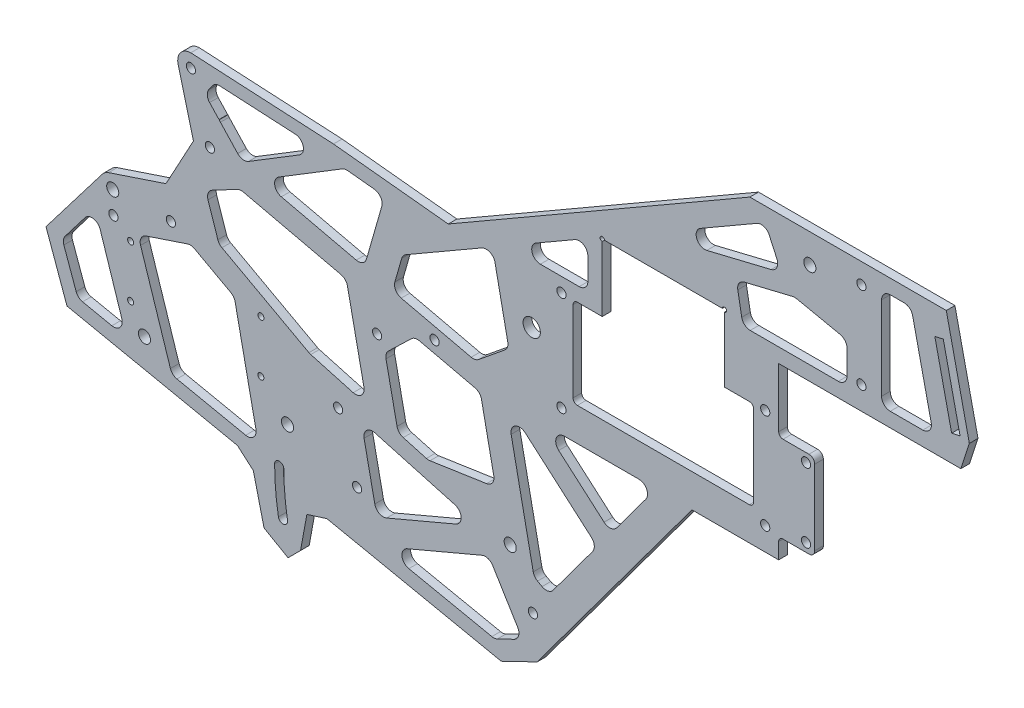
SolidWorks part; units mm, degrees
material "6061 Alloy"
ref_plane "Front Plane" through (0, 0, 0) normal (0, 0, 1) x (1, 0, 0)
ref_plane "Top Plane" through (0, 0, 0) normal (0, 1, 0) x (1, 0, 0)
ref_plane "Right Plane" through (0, 0, 0) normal (1, 0, 0) x (0, 0, -1)
sketch "Sketch1" plane through (0, 0, 0) normal (0, 0, 1) x (1, 0, 0)
  line L1 (-20.4587, 47.6) -> (-183.6375, 47.6)
  line L2 (-20.4587, 47.6) -> (-20.4587, -36.0143)
  line L3 (-20.4587, -36.0143) -> (-183.6375, -36.0143)
  line L4 (-183.6375, 47.6) -> (-183.6375, -36.0143)
extrude "Boss-Extrude1" add sketch "Sketch1" along normal blind 3
sketch "Sketch2" plane through (0, 0, 3) normal (0, 0, 1) x (1, 0, 0)
  circle A0 centre (-24.2887, 24) radius 3
  dimension "D1" = 6
extrude "Cut-Extrude1" cut sketch "Sketch2" against normal blind 70
sketch "Sketch3" plane through (0, 0, 3) normal (0, 0, 1) x (1, 0, 0)
  line L4 (-20.4587, -36.0143) -> (-20.4587, 47.6)
  line L5 (-20.4587, 47.6) -> (-183.6375, 47.6)
  line L6 (-183.6375, 47.6) -> (-183.6375, -36.0143)
  line L7 (-183.6375, -36.0143) -> (-20.4587, -36.0143)
  line L8 (-20.4587, -36.0143) -> (-20.4587, 47.6)
  line L9 (-20.4587, 47.6) -> (-41.1202, 47.6)
  line L10 (-183.6375, 47.6) -> (-183.6375, -36.0143)
  line L11 (-183.6375, -36.0143) -> (-20.4587, -36.0143)
  line L13 (51.3713, 101) -> (-41.1202, 47.6)
  line L14 (-41.1202, 47.6) -> (-120.7247, 47.6)
  line L15 (-204.873, 47.6) -> (-204.873, -81.5667)
  line L16 (-204.873, -81.5667) -> (-34.873, -81.5667)
  line L17 (-34.873, -81.5667) -> (61.3713, -26)
  line L18 (61.3713, -26) -> (61.3713, 2.5)
  line L19 (62.8713, 4) -> (71.8713, 4)
  line L20 (73.8713, 6) -> (73.8713, 32)
  line L21 (71.8713, 34) -> (62.8713, 34)
  line L22 (61.3713, 35.5) -> (61.3713, 56)
  line L23 (61.3713, 56) -> (121.3713, 56)
  line L24 (121.3713, 56) -> (121.3713, 101)
  line L25 (121.3713, 101) -> (51.3713, 101)
  line L26 (51.3713, 101) -> (-41.1202, 47.6)
  line L27 (-167.8527, 47.6) -> (-120.7247, 47.6)
  line L28 (-204.873, 47.6) -> (-204.873, -81.5667)
  line L29 (-204.873, -81.5667) -> (-34.873, -81.5667)
  line L30 (-34.873, -81.5667) -> (61.3713, -26)
  line L31 (61.3713, -26) -> (61.3713, 2.5)
  line L32 (62.8713, 4) -> (71.8713, 4)
  line L33 (73.8713, 6) -> (73.8713, 32)
  line L34 (71.8713, 34) -> (62.8713, 34)
  line L35 (61.3713, 35.5) -> (61.3713, 56)
  line L36 (61.3713, 56) -> (121.3713, 56)
  line L37 (121.3713, 56) -> (121.3713, 101)
  line L38 (121.3713, 101) -> (51.3713, 101)
  line L265 (-167.8527, 47.6) -> (-204.873, 47.6)
  line L266 (-183.6375, 47.6) -> (-204.873, 47.6)
  circle A0 centre (70.8713, 31) radius 1.6 construction
  circle A1 centre (70.8713, 7) radius 1.6 construction
  arc A2 (71.8713, 4) -> (73.8713, 6) centre (71.8713, 6) ccw
  arc A3 (73.8713, 32) -> (71.8713, 34) centre (71.8713, 32) ccw
  arc A4 (71.8713, 4) -> (73.8713, 6) centre (71.8713, 6) ccw
  arc A5 (73.8713, 32) -> (71.8713, 34) centre (71.8713, 32) ccw
  circle A6 centre (70.8713, 31) radius 1.6
  circle A7 centre (70.8713, 7) radius 1.6
  arc A38 (62.8713, 4) -> (61.3713, 2.5) centre (62.8713, 2.5) ccw
  arc A39 (62.8713, 4) -> (61.3713, 2.5) centre (62.8713, 2.5) ccw
  arc A40 (61.3713, 35.5) -> (62.8713, 34) centre (62.8713, 35.5) ccw
  arc A41 (61.3713, 35.5) -> (62.8713, 34) centre (62.8713, 35.5) ccw
  arc A60 (-120.7247, 47.6) -> (-167.8527, 47.6) centre (-144.2887, 24) ccw
  arc A61 (-120.7247, 47.6) -> (-167.8527, 47.6) centre (-144.2887, 24) ccw
  dimension "D1" = 0
  dimension "D2" = 0
extrude "Boss-Extrude2" add sketch "Sketch3" against normal blind 3
sketch "Sketch4" plane through (0, 0, 3) normal (0, 0, 1) x (1, 0, 0)
  line L0 (0.1713, 62.05) -> (0.1713, 39.5) construction
  line L2 (-9.9587, 10) -> (-9.9587, 38) construction
  line L3 (-8.4587, 8.5) -> (51.2013, 8.5) construction
  line L4 (52.7013, 10) -> (52.7013, 38) construction
  line L7 (41.8213, 62.8) -> (0.9213, 62.8) construction
  line L8 (0.1713, 62.05) -> (0.1713, 39.5)
  line L9 (-8.4587, 39.5) -> (0.1713, 39.5)
  line L10 (-9.9587, 10) -> (-9.9587, 38)
  line L11 (-8.4587, 8.5) -> (51.2013, 8.5)
  line L12 (52.7013, 10) -> (52.7013, 38)
  line L13 (42.5713, 39.5) -> (51.2013, 39.5)
  line L14 (42.5713, 62.05) -> (42.5713, 39.5)
  line L15 (41.8213, 62.8) -> (0.9213, 62.8)
  arc A1 (-8.4587, 39.5) -> (-9.9587, 38) centre (-8.4587, 38) ccw construction
  arc A2 (-9.9587, 10) -> (-8.4587, 8.5) centre (-8.4587, 10) ccw construction
  arc A3 (51.2013, 8.5) -> (52.7013, 10) centre (51.2013, 10) ccw construction
  arc A4 (52.7013, 38) -> (51.2013, 39.5) centre (51.2013, 38) ccw construction
  arc A5 (42.5713, 62.05) -> (41.8213, 62.8) centre (42.5713, 62.8) ccw construction
  arc A6 (0.9213, 62.8) -> (0.1713, 62.05) centre (0.1713, 62.8) ccw
  arc A7 (-8.4587, 39.5) -> (-9.9587, 38) centre (-8.4587, 38) ccw
  arc A8 (-9.9587, 10) -> (-8.4587, 8.5) centre (-8.4587, 10) ccw
  arc A9 (51.2013, 8.5) -> (52.7013, 10) centre (51.2013, 10) ccw
  arc A10 (52.7013, 38) -> (51.2013, 39.5) centre (51.2013, 38) ccw
  arc A11 (42.5713, 62.05) -> (41.8213, 62.8) centre (42.5713, 62.8) ccw
extrude "Cut-Extrude2" cut sketch "Sketch4" against normal blind 10
sketch "Sketch6" plane through (0, 0, 0) normal (0, 0, -1) x (-1, 0, 0)
  line L0 (-121.3713, 101) -> (-51.3713, 101) construction
  line L1 (-121.3713, 56) -> (-121.3713, 101) construction
  line L2 (204.873, -81.5667) -> (34.873, -81.5667) construction
  line L3 (-61.3713, -26) -> (-61.3713, 2.5) construction
  line L4 (204.873, 47.6) -> (204.873, -81.5667) construction
  circle A2 centre (158.6381, -45.9257) radius 2.1
  circle A3 centre (169.6384, -7.2338) radius 2.1
  circle A4 centre (109.0119, -47.5134) radius 2.1
  circle A5 centre (31.7556, -45.033) radius 2.1
  circle A6 centre (-71.9717, 91) radius 2.1
  dimension "D1" = 10
  dimension "D2" = 49.3996
  dimension "D3" = 36.5337
  dimension "D4" = 93.1269
  dimension "D5" = 34.0533
  dimension "D6" = 95.8611
  dimension "D7" = 35.641
  dimension "D8" = 46.2349
  dimension "D9" = 35.2346
  dimension "D10" = 74.3329
  dimension "D11" = 4.2
extrude "Cut-Extrude3" cut sketch "Sketch6" against normal blind 10
sketch "Sketch7" plane through (0, 0, 3) normal (0, 0, 1) x (1, 0, 0)
  circle A0 centre (56.7013, 5) radius 1.6
  circle A1 centre (-13.9587, 5) radius 1.6
  circle A2 centre (56.7013, 39.6) radius 1.6
  circle A3 centre (-13.9587, 39.6) radius 1.6
  dimension "D1" = 3.2
extrude "Cut-Extrude4" cut sketch "Sketch7" against normal blind 10
sketch "Sketch8" plane through (0, 0, 0) normal (0, 0, -1) x (-1, 0, 0)
  circle A0 centre (163.4287, -37.6667) radius 1.05
  circle A1 centre (163.4287, -19.6667) radius 1.05
  circle A2 centre (118.2287, -37.6667) radius 1.05
  circle A3 centre (118.2287, -19.6667) radius 1.05
  dimension "D1" = 2.1
extrude "Cut-Extrude5" cut sketch "Sketch8" against normal blind 10
sketch "Sketch9" plane through (0, 0, 0) normal (0, 0, -1) x (-1, 0, 0)
  line L0 (-118.4267, 56) -> (-121.3713, 65.0628)
  line L1 (-61.3713, 56) -> (-121.3713, 56) construction
  line L2 (-121.3713, 65.0628) -> (-121.3713, 56)
  line L3 (-121.3713, 56) -> (-118.4267, 56)
  line L4 (-121.3713, 65.0628) -> (-113.3713, 101)
  line L5 (-113.3713, 101) -> (-121.3713, 101)
  line L6 (-121.3713, 101) -> (-121.3713, 65.0628)
  line L7 (-17.2669, -51.4637) -> (-61.3713, 0.5)
  line L8 (34.873, -81.5667) -> (-61.3713, -26) construction
  line L9 (-61.3713, 0.5) -> (-61.3713, -26)
  line L10 (-61.3713, -26) -> (-17.2669, -51.4637)
  line L11 (104.2003, -81.5667) -> (102.2857, -71.1635)
  line L12 (102.2857, -71.1635) -> (95.3446, -68.9652)
  line L13 (95.3446, -68.9652) -> (34.873, -81.5667)
  line L14 (34.873, -81.5667) -> (104.2003, -81.5667)
  line L15 (117.4045, -81.5667) -> (120.8632, -67.2922)
  line L16 (204.873, -81.5667) -> (34.873, -81.5667) construction
  line L17 (120.8632, -67.2922) -> (126.3485, -62.5044)
  line L18 (126.3485, -62.5044) -> (185.4974, -50.1785)
  line L19 (185.4974, -50.1785) -> (192.7819, -29.967)
  line L20 (192.7819, -29.967) -> (177.6384, -10.1551)
  line L21 (177.6384, -10.1551) -> (177.6384, 23.9998)
  line L22 (177.6384, 23.9998) -> (204.873, 23.9998)
  line L23 (204.873, 47.6) -> (204.873, -81.5667) construction
  line L24 (204.873, 23.9998) -> (204.873, -81.5667)
  line L25 (204.873, -81.5667) -> (117.4045, -81.5667)
  line L26 (-50.2448, 61) -> (-83.5713, 61)
  line L28 (-85.0713, 62.5) -> (-85.0713, 73.769)
  line L30 (-83.9897, 75.2094) -> (-66.2924, 80.35)
  line L32 (-65.5204, 80.3673) -> (-47.7224, 76.05)
  line L34 (-46.5996, 74.3275) -> (-48.7684, 62.2352)
  line L36 (-25.3142, 76.7885) -> (-59.5197, 85.0857)
  line L38 (-60.5306, 87.1663) -> (-56.3939, 96.2292)
  line L40 (-54.2793, 96.9054) -> (-24.2105, 79.5452)
  line L41 (9.9587, 10) -> (9.9587, 38) construction
  line L42 (-51.2013, 8.5) -> (8.4587, 8.5) construction
  arc A0 (-48.7684, 62.2352) -> (-50.2448, 61) centre (-50.2448, 62.5) cw
  arc A1 (-46.5996, 74.3275) -> (-47.7224, 76.05) centre (-48.076, 74.5923) ccw
  arc A2 (-83.5713, 61) -> (-85.0713, 62.5) centre (-83.5713, 62.5) cw
  arc A3 (-85.0713, 73.769) -> (-83.9897, 75.2094) centre (-83.5713, 73.769) cw
  arc A4 (-65.5204, 80.3673) -> (-66.2924, 80.35) centre (-65.874, 78.9096) ccw
  arc A5 (-25.3142, 76.7885) -> (-24.2105, 79.5452) centre (-24.9605, 78.2462) ccw
  arc A6 (-59.5197, 85.0857) -> (-60.5306, 87.1663) centre (-59.1661, 86.5434) cw
  arc A7 (-54.2793, 96.9054) -> (-56.3939, 96.2292) centre (-55.0293, 95.6064) ccw
  line M29 (204.873, -81.5667) -> (204.873, 47.6)
  line M34 (-51.3713, 101) -> (-121.3713, 101)
  line M35 (-121.3713, 101) -> (-121.3713, 56)
  line M36 (-121.3713, 56) -> (-61.3713, 56)
  line M45 (-61.3713, 2.5) -> (-61.3713, -26)
  line M46 (-61.3713, -26) -> (34.873, -81.5667)
  line M47 (34.873, -81.5667) -> (204.873, -81.5667)
  dimension "D1" = 1.5
  dimension "D2" = 85.3859
  dimension "D3" = 92.327
  dimension "D4" = 94.2416
  dimension "D5" = 107.4459
  dimension "D6" = 110.9045
  dimension "D7" = 116.3898
  dimension "D8" = 167.6797
  dimension "D9" = 34.1692
  dimension "D10" = 175.5387
  dimension "D11" = 182.8232
  dimension "D12" = 27.2256
  dimension "D13" = 34.9192
  dimension "D14" = 35.2728
  dimension "D15" = 56.5583
  dimension "D16" = 57.6811
  dimension "D17" = 58.0347
  dimension "D18" = 58.7271
  dimension "D19" = 64.238
  dimension "D20" = 66.3526
  dimension "D21" = 75.4791
  dimension "D22" = 76.2511
  dimension "D23" = 93.9484
  dimension "D24" = 15.4998
  dimension "D25" = 52.5
  dimension "D26" = 68.2885
  dimension "D27" = 56.5628
  dimension "D28" = 58.6785
  dimension "D29" = 75.7922
  dimension "D32" = 123.33
  dimension "D33" = 128.3853
  dimension "D47" = 8
  dimension "D48" = 18.6551
  dimension "D49" = 38.467
extrude "Cut-Extrude6" cut sketch "Sketch9" against normal blind 10 contours L22 L21 L20 L19 L18 L17 L15 M47 M29 | L12 L13 L11 M47 | L7 M46 M45 | L32 A4 L30 A3 L28 A2 L26 A0 L34 A1 | L40 A7 L38 A6 L36 A5 | L0 M36 M35 | L4 M35 M34 region at (120.3898, 59.0209, 0) region at (118.7047, 89.0209, 0) region at (46.6698, -25.6546, 0) region at (-120.4662, -74.7523, 0) region at (-79.7621, -77.1158, 0) region at (66.1251, 69.6249, 0) region at (44.9534, 86.2187, 0)
sketch "Sketch10" plane through (0, 0, 3) normal (0, 0, 1) x (1, 0, 0)
  line L0 (17.2669, -51.4637) -> (10.2058, -59.7831)
  line L1 (10.2058, -59.7831) -> (-34.873, -81.5667)
  line L2 (-34.873, -81.5667) -> (17.2669, -51.4637)
  line L3 (-9.9587, 38) -> (-9.9587, 10) construction
  line L4 (-8.4587, 8.5) -> (51.2013, 8.5) construction
  dimension "D1" = 20.1645
  dimension "D2" = 68.2831
extrude "Boss-Extrude3" add sketch "Sketch10" against normal blind 3
sketch "Sketch11" plane through (0, 0, 0) normal (0, 0, -1) x (-1, 0, 0)
  line L0 (182.0256, -45.065) -> (186.8761, -31.6065)
  line L1 (204.873, 47.6) -> (204.873, 23.9998) construction
  line L2 (186.6567, -30.187) -> (177.4937, -18.1993)
  line L3 (-113.3713, 101) -> (-51.3713, 101) construction
  line L4 (174.8756, -18.6461) -> (165.68, -46.9072)
  line L6 (167.4124, -48.8398) -> (180.9204, -46.0249)
  arc A0 (112.1618, -76.8394) -> (109.0086, -76.294) centre (110.5852, -76.5667) cw
  arc A1 (112.1618, -76.8394) -> (113.473, -61.5667) centre (23.873, -61.5667) ccw
  arc A2 (110.273, -61.5667) -> (109.0086, -76.294) centre (23.873, -61.5667) cw
  arc A3 (113.473, -61.5667) -> (110.273, -61.5667) centre (111.873, -61.5667) ccw
  circle A4 centre (23.873, -61.5667) radius 1.6
  arc A5 (180.9204, -46.0249) -> (182.0256, -45.065) centre (180.6144, -44.5564) ccw
  arc A6 (186.8761, -31.6065) -> (186.6567, -30.187) centre (185.465, -31.0979) ccw
  arc A7 (177.4937, -18.1993) -> (174.8756, -18.6461) centre (176.302, -19.1102) ccw
  arc A8 (167.4124, -48.8398) -> (165.68, -46.9072) centre (167.1064, -47.3713) cw
  dimension "D1" = 1.6
  dimension "D2" = 89.6
  dimension "D3" = 17.9969
  dimension "D4" = 1.5
  dimension "D5" = 18.2163
  dimension "D6" = 19.408
  dimension "D7" = 22.8475
  dimension "D8" = 23.9526
  dimension "D9" = 27.3793
  dimension "D10" = 29.9974
  dimension "D11" = 92.7112
  dimension "D12" = 93
  dimension "D13" = 119.1993
  dimension "D14" = 162.5667
extrude "Cut-Extrude7" cut sketch "Sketch11" against normal blind 3
sketch "Sketch12" plane through (0, 0, 0) normal (0, 0, -1) x (-1, 0, 0)
  line L0 (204.873, 47.6) -> (204.873, 23.9998) construction
  line L1 (-113.3713, 101) -> (-51.3713, 101) construction
  circle A0 centre (-90.0713, 94) radius 1.6
  circle A1 centre (-90.0713, 64) radius 1.6
  dimension "D1" = 3.2
  dimension "D2" = 294.9443
  dimension "D3" = 7
  dimension "D4" = 37
extrude "Cut-Extrude8" cut sketch "Sketch12" against normal blind 3
sketch "Sketch15" plane through (0, 0, 3) normal (0, 0, 1) x (1, 0, 0)
  line L0 (-104.2003, -81.5667) -> (-117.4045, -81.5667)
  line L1 (-117.4045, -81.5667) -> (-117.1382, -82.6658)
  line L2 (-117.1382, -82.6658) -> (-108.8293, -87.4629)
  line L3 (-108.8293, -87.4629) -> (-104.4861, -83.1198)
  line L4 (-104.4861, -83.1198) -> (-104.2003, -81.5667)
  line L5 (52.7013, 10) -> (52.7013, 38) construction
  line L6 (41.8213, 62.8) -> (0.9213, 62.8) construction
  dimension "D1" = 157.1875
  dimension "D2" = 161.5306
  dimension "D3" = 169.8396
  dimension "D4" = 145.4658
  dimension "D5" = 145.9198
  dimension "D6" = 150.2629
extrude "Boss-Extrude4" add sketch "Sketch15" against normal blind 3
sketch "Sketch16" plane through (0, 0, 0) normal (0, 0, -1) x (-1, 0, 0)
  line L0 (11.2698, -56.8332) -> (-11.3083, -45.9227)
  line L1 (0.4601, -6.3291) -> (-30.5111, -21.7344)
  line L2 (-11.7993, -45.5427) -> (-23.6576, -31.5713)
  line L3 (204.873, 47.6) -> (204.873, 23.9998) construction
  line L4 (-23.182, -29.2577) -> (27.4491, -4.0733)
  line L5 (-32.3227, -21.3621) -> (-41.0149, -11.1209)
  line L6 (29.5868, -5.7168) -> (22.3602, -41.0637)
  line L7 (-61.3713, 56) -> (-118.4267, 56) construction
  line L8 (22.1716, -41.5438) -> (13.2034, -56.2631)
  line L9 (-41.3713, -10.1503) -> (-41.3713, -1)
  line L11 (-39.8713, 0.5) -> (-2.7749, 0.5)
  line L13 (-1.5138, -0.1879) -> (1.0532, -4.174)
  arc A0 (13.2034, -56.2631) -> (11.2698, -56.8332) centre (11.9225, -55.4826) cw
  arc A1 (22.1716, -41.5438) -> (22.3602, -41.0637) centre (20.8906, -40.7633) ccw
  arc A2 (29.5868, -5.7168) -> (27.4491, -4.0733) centre (28.1172, -5.4164) ccw
  arc A3 (-11.3083, -45.9227) -> (-11.7993, -45.5427) centre (-10.6557, -44.5721) cw
  arc A4 (-23.6576, -31.5713) -> (-23.182, -29.2577) centre (-22.514, -30.6007) cw
  arc A5 (0.4601, -6.3291) -> (1.0532, -4.174) centre (-0.208, -4.9861) ccw
  arc A6 (-1.5138, -0.1879) -> (-2.7749, 0.5) centre (-2.7749, -1) ccw
  arc A7 (-30.5111, -21.7344) -> (-32.3227, -21.3621) centre (-31.1791, -20.3914) cw
  arc A8 (-41.0149, -11.1209) -> (-41.3713, -10.1503) centre (-39.8713, -10.1503) cw
  arc A9 (-41.3713, -1) -> (-39.8713, 0.5) centre (-39.8713, -1) cw
  dimension "D1" = 1.5
  dimension "D2" = 175.2862
  dimension "D3" = 176.7558
  dimension "D4" = 177.4239
  dimension "D5" = 182.5128
  dimension "D6" = 182.7014
  dimension "D7" = 191.6696
  dimension "D8" = 193.6032
  dimension "D9" = 203.8199
  dimension "D10" = 204.413
  dimension "D11" = 205.081
  dimension "D12" = 206.3868
  dimension "D13" = 215.5287
  dimension "D14" = 216.6723
  dimension "D15" = 235.3841
  dimension "D16" = 245.888
  dimension "D17" = 55.5
extrude "Cut-Extrude11" cut sketch "Sketch16" against normal blind 3
sketch "Sketch18" plane through (0, 0, 0) normal (0, 0, -1) x (-1, 0, 0)
  line L0 (7.0787, 61.4804) -> (31.6415, 47.299)
  line L1 (-52.7013, 38) -> (-52.7013, 10) construction
  line L2 (30.8915, 44.5) -> (6.3287, 44.5)
  line L3 (-0.9213, 62.8) -> (-41.8213, 62.8) construction
  line L4 (4.8287, 46) -> (4.8287, 60.1813)
  arc A0 (4.8287, 60.1813) -> (7.0787, 61.4804) centre (6.3287, 60.1813) cw
  arc A1 (4.8287, 46) -> (6.3287, 44.5) centre (6.3287, 46) ccw
  arc A2 (31.6415, 47.299) -> (30.8915, 44.5) centre (30.8915, 46) cw
  dimension "D1" = 1.5
  dimension "D2" = 57.53
  dimension "D3" = 59.78
  dimension "D4" = 83.5928
  dimension "D5" = 1.3196
extrude "Cut-Extrude13" cut sketch "Sketch18" against normal blind 3
sketch "Sketch19" plane through (0, 0, 3) normal (0, 0, 1) x (1, 0, 0)
  line L0 (52.7013, 10) -> (52.7013, 38) construction
  line L1 (41.8213, 62.8) -> (0.9213, 62.8) construction
  circle A0 centre (-91.4566, -33.7689) radius 1.6
  circle A1 centre (-77.9328, -4.7671) radius 1.6
  circle A2 centre (-149.4603, -6.7213) radius 1.6
  circle A3 centre (-135.9365, 22.2805) radius 1.6
  dimension "D1" = 3.2
  dimension "D2" = 130.6341
  dimension "D3" = 144.1579
  dimension "D4" = 188.6378
  dimension "D5" = 202.1616
  dimension "D6" = 40.5195
  dimension "D7" = 67.5671
  dimension "D8" = 69.5213
  dimension "D9" = 96.5689
extrude "Cut-Extrude14" cut sketch "Sketch19" against normal blind 3
sketch "Sketch20" plane through (0, 0, 3) normal (0, 0, 1) x (1, 0, 0)
  line L0 (-87.4344, -49.9884) -> (-62.9225, 2.5774) construction
  line L1 (-87.4344, -49.9884) -> (-164.4705, -14.0659) construction
  line L2 (-62.9225, 2.5774) -> (-139.9587, 38.5) construction
  line L3 (-164.4705, -14.0659) -> (-139.9587, 38.5) construction
  line L6 (-87.4344, -49.9884) -> (-139.9587, 38.5) construction
  line L7 (-62.9225, 2.5774) -> (-164.4705, -14.0659) construction
  line L8 (52.7013, 10) -> (52.7013, 38) construction
  line L9 (41.8213, 62.8) -> (0.9213, 62.8) construction
  circle A0 centre (-84.8823, -54.288) radius 1.6
  circle A1 centre (-169.4047, -14.8745) radius 1.6
  circle A2 centre (-57.9884, 3.3861) radius 1.6
  circle A3 centre (-142.5108, 42.7996) radius 1.6
  dimension "D1" = 3.2
  dimension "D2" = 5
  dimension "D3" = 5
  dimension "D4" = 5
  dimension "D5" = 5
  dimension "D6" = 110.6897
  dimension "D7" = 137.5836
  dimension "D8" = 195.2122
  dimension "D9" = 222.1061
  dimension "D10" = 20.0004
extrude "Cut-Extrude15" cut sketch "Sketch20" against normal blind 3
sketch "Sketch22" plane through (0, 0, 3) normal (0, 0, 1) x (1, 0, 0)
  line L0 (-37.1234, -75.9903) -> (-76.3231, -67.8216)
  line L1 (-37.1234, -75.9903) -> (-27.4515, -71.3165)
  line L2 (-27.4515, -71.3165) -> (-39.179, -52.0683)
  line L3 (-42.6859, -44.8659) -> (-83.4484, -33.5518)
  line L4 (-83.4484, -33.5518) -> (-77.9834, -59.8361)
  line L5 (-119.0289, -58.9223) -> (-149.0861, -52.6587)
  line L6 (-149.0861, -52.6587) -> (-160.8985, -16.3554)
  line L7 (-160.8985, -16.3554) -> (-142.4426, -10.2002)
  line L8 (-142.4426, -10.2002) -> (-127.4625, -18.3601)
  line L9 (-127.4625, -18.3601) -> (-119.0289, -58.9223)
  line L10 (-60.2062, -33.7761) -> (-36.8146, -30.2729)
  line L11 (-36.8146, -30.2729) -> (-42.1035, -4.4033)
  line L12 (-42.1035, -4.4033) -> (-64.8597, 0.8733)
  line L13 (-64.8597, 0.8733) -> (-75.1752, -9.0737)
  line L14 (-75.1752, -9.0737) -> (-70.6413, -30.8797)
  line L15 (-70.6413, -30.8797) -> (-60.2062, -33.7761)
  line L16 (-81.4807, -27.8711) -> (-88.6019, 6.3786)
  line L17 (-88.6019, 6.3786) -> (-125.4554, 14.9242)
  line L18 (-125.4554, 14.9242) -> (-137.3952, 8.5985)
  line L19 (-137.3952, 8.5985) -> (-132.7901, -5.2095)
  line L20 (-132.7901, -5.2095) -> (-101.2724, -22.3777)
  line L21 (-101.2724, -22.3777) -> (-81.4807, -27.8711)
  line L22 (-43.8661, 4.2176) -> (-32.2369, 13.699)
  line L23 (-32.2369, 13.699) -> (-37.5323, 39.6)
  line L24 (-37.5323, 39.6) -> (-64.3985, 39.6)
  line L25 (-64.3985, 39.6) -> (-72.6338, 10.8882)
  line L26 (-72.6338, 10.8882) -> (-43.8661, 4.2176)
  line L28 (-82.3882, 13.1501) -> (-74.8017, 39.6)
  line L29 (-74.8017, 39.6) -> (-129.552, 39.6)
  line L30 (-129.552, 39.6) -> (-133.929, 33.4456)
  line L31 (-133.929, 33.4456) -> (-124.0034, 22.7997)
  line L32 (-124.0034, 22.7997) -> (-82.3882, 13.1501)
  line L33 (-171.088, -2.8873) -> (-151.1667, 3.7566)
  line L34 (-151.1667, 3.7566) -> (-141.6423, 21.3231)
  line L35 (-141.6423, 21.3231) -> (-146.9443, 41.6428)
  line L36 (-167.4124, -48.8398) -> (-180.9204, -46.0249) construction
  line L37 (-173.2787, -4.4514) -> (-177.6384, -10.1551)
  line L38 (-34.873, -81.5667) -> (10.2058, -59.7831) construction
  line L39 (-13.2034, -56.2631) -> (-22.1716, -41.5438) construction
  line L40 (-39.179, -52.0683) -> (-76.3231, -67.8216)
  line L41 (-42.6859, -44.8659) -> (-77.9834, -59.8361)
  line L42 (-142.5567, 47.3813) -> (-120.7247, 47.6)
  line L43 (-192.7819, -29.967) -> (-177.6384, -10.1551) construction
  line L44 (-142.5108, 42.7996) -> (-169.6384, -7.2338) construction
  line L45 (-22.3602, -41.0637) -> (-29.5868, -5.7168) construction
  line L46 (-41.1202, 47.6) -> (-120.7247, 47.6) construction
  line L47 (-174.8756, -18.6461) -> (-165.68, -46.9072) construction
  line L48 (-120.7247, 47.6) -> (-129.552, 69.989)
  line L49 (-129.552, 69.989) -> (-217.9731, 55.7464)
  line L50 (-217.9731, 55.7464) -> (-212.0666, -12.7046)
  line L51 (-212.0666, -12.7046) -> (-177.6384, -10.1551)
  circle A0 centre (-169.6384, -7.2338) radius 4.5819
  circle A1 centre (-142.5108, 42.7996) radius 4.5819
  circle A2 centre (-57.9884, 3.3861) radius 1.6 construction
  point P63 (-65.4238, -32.3279)
  dimension "D16" = 4
  dimension "D1" = 11
  dimension "D2" = 8
  dimension "D3" = 6
  dimension "D4" = 20
  dimension "D5" = 6
  dimension "D6" = 12
  dimension "D7" = 8
  dimension "D8" = 8
  dimension "D9" = 10
  dimension "D10" = 10
  dimension "D11" = 21
  dimension "D12" = 14
  dimension "D13" = 40
  dimension "D14" = 9
  dimension "D15" = 16
extrude "Cut-Extrude16" cut sketch "Sketch22" against normal blind 10 contours L2 L40 L0 L1 | L41 L3 L4 | L14 L15 L10 L11 L12 L13 | L25 L26 L22 L23 L24 | L20 L21 L16 L17 L18 L19 | L9 L8 L7 L6 L5 | L31 L32 L28 L29 L30 | L44 L35 A1 L42 L48 L49 L50 L51 L37 A0 L33 | L35 L44 L33 L34 region at (-47.4966, -65.535, 3) region at (-68.0392, -46.0846, 3) region at (-139.3463, -34.1696, 3) region at (-56.4198, -17.2748, 3) region at (-107.6566, -4.2679, 3) region at (-51.5948, 22.5538, 3) region at (-102.033, 29.198, 3) region at (-178.9177, 31.6695, 3) region at (-151.8367, 15.4851, 3)
fillet "Fillet2" radius 3 34 edges at (-37.5323, 39.6, 1.5) (-64.3985, 39.6, 1.5) (-32.2369, 13.699, 1.5) (-43.8661, 4.2176, 1.5) (-82.3882, 13.1501, 1.5) (-72.6338, 10.8882, 1.5) (-124.0034, 22.7997, 1.5) (-132.7901, -5.2095, 1.5) (-101.2724, -22.3777, 1.5) (-81.4807, -27.8711, 1.5) (-133.929, 33.4456, 1.5) (-129.552, 39.6, 1.5) (-137.3952, 8.5985, 1.5) (-160.8985, -16.3554, 1.5) (-88.6019, 6.3786, 1.5) (-74.8017, 39.6, 1.5) (-125.4554, 14.9242, 1.5) (-142.4426, -10.2002, 1.5) (-127.4625, -18.3601, 1.5) (-119.0289, -58.9223, 1.5) (-149.0861, -52.6587, 1.5) (-70.6413, -30.8797, 1.5) (-60.2062, -33.7761, 1.5) (-42.1035, -4.4033, 1.5) (-36.8146, -30.2729, 1.5) (-64.8597, 0.8733, 1.5) (-75.1752, -9.0737, 1.5) (-83.4484, -33.5518, 1.5) (-77.9834, -59.8361, 1.5) (-76.3231, -67.8216, 1.5) (-39.179, -52.0683, 1.5) (-42.6859, -44.8659, 1.5) (-37.1234, -75.9903, 1.5) (-27.4515, -71.3165, 1.5)
sketch "Sketch23" plane through (0, 0, 3) normal (0, 0, 1) x (1, 0, 0)
  line L0 (-15.1302, -62.3797) -> (12.2183, -50.6967)
  line L1 (12.2183, -50.6967) -> (46.1657, -12.476)
  line L2 (46.1657, -12.476) -> (46.1657, 2.4504)
  line L3 (46.1657, 2.4504) -> (-9.1293, 2.4504)
  line L4 (-9.1293, 2.4504) -> (-16.2227, -2.8307)
  line L5 (-16.2227, -2.8307) -> (-26.155, 1.2793)
  line L6 (-26.155, 1.2793) -> (-39.1064, -4.2534)
  line L7 (-39.1064, -4.2534) -> (-15.1302, -62.3797)
  line L8 (85.0713, 62.5) -> (85.0713, 73.769) construction
  line L9 (113.3713, 101) -> (51.3713, 101) construction
  line L10 (61.3713, 0.5) -> (52.8467, -9.5437)
  line L11 (17.2669, -51.4637) -> (61.3713, 0.5) construction
  line L12 (52.8467, -9.5437) -> (61.3713, -9.5437)
  line L13 (61.3713, -9.5437) -> (61.3713, 0.5)
  dimension "D1" = 38.9056
  dimension "D2" = 72.853
  dimension "D3" = 94.2006
  dimension "D4" = 100.2015
  dimension "D5" = 101.294
  dimension "D6" = 111.2263
  dimension "D7" = 124.1778
  dimension "D8" = 98.5496
  dimension "D9" = 99.7207
  dimension "D10" = 103.8307
  dimension "D11" = 105.2534
  dimension "D12" = 113.476
  dimension "D13" = 151.6967
extrude "Boss-Extrude5" add sketch "Sketch23" against normal blind 3
sketch "Sketch24" plane through (0, 0, 3) normal (0, 0, 1) x (1, 0, 0)
  line L0 (61.3713, -3) -> (31.2918, -3)
  line L1 (31.2918, -3) -> (-22.4178, -75.5479)
  line L2 (-22.4178, -75.5479) -> (68.0776, -67.6539)
  line L3 (68.0776, -67.6539) -> (61.3713, -3)
  line L4 (-17.6291, -52.2733) -> (-2.3415, -31.6237)
  line L5 (2.0346, -22.9964) -> (-17.9678, -5.6327)
  line L6 (-2.5637, -29.5984) -> (-29.8659, -5.898)
  line L7 (85.0713, 62.5) -> (85.0713, 73.769) construction
  line L8 (-32.3188, -7.3312) -> (-23.6278, -49.8413)
  line L9 (-16.9844, -3) -> (15.8728, -3)
  line L10 (-22.8847, -50.8531) -> (-19.5612, -52.6931)
  line L11 (113.3713, 101) -> (51.3713, 101) construction
  line L12 (17.0783, -5.3925) -> (4.2235, -22.7562)
  arc A0 (-19.5612, -52.6931) -> (-17.6291, -52.2733) centre (-18.8346, -51.3808) ccw
  arc A1 (-22.8847, -50.8531) -> (-23.6278, -49.8413) centre (-22.1582, -49.5408) cw
  arc A2 (-32.3188, -7.3312) -> (-29.8659, -5.898) centre (-30.8492, -7.0307) cw
  arc A3 (-2.3415, -31.6237) -> (-2.5637, -29.5984) centre (-3.547, -30.7312) ccw
  arc A4 (2.0346, -22.9964) -> (4.2235, -22.7562) centre (3.0089, -21.7818) ccw
  arc A5 (-17.9678, -5.6327) -> (-16.9844, -3) centre (-16.9844, -4.5) cw
  arc A6 (15.8728, -3) -> (17.0783, -5.3925) centre (15.8728, -4.5) cw
  dimension "D1" = 1.5
  dimension "D2" = 1.5571
  dimension "D3" = 16.9937
  dimension "D4" = 23.7
  dimension "D5" = 53.7795
  dimension "D6" = 67.993
  dimension "D7" = 69.1986
  dimension "D8" = 80.8479
  dimension "D9" = 82.0624
  dimension "D10" = 83.0367
  dimension "D11" = 87.4128
  dimension "D12" = 87.6351
  dimension "D13" = 102.0558
  dimension "D14" = 102.7004
  dimension "D15" = 104.6325
  dimension "D16" = 107.2295
  dimension "D17" = 108.6991
  dimension "D18" = 104
  dimension "D20" = 107.4891
  dimension "D38" = 168.6539
  dimension "D39" = 176.5479
extrude "Cut-Extrude17" cut sketch "Sketch24" against normal blind 3
sketch "Sketch25" plane through (0, 0, 3) normal (0, 0, 1) x (1, 0, 0)
  line L0 (87.5622, 58.5714) -> (87.5622, 78.331)
  line L1 (87.5622, 78.331) -> (64.471, 87.209)
  line L2 (64.471, 87.209) -> (55.9377, 98.9782)
  line L3 (55.9377, 98.9782) -> (45.5782, 95.3423)
  line L4 (45.5782, 95.3423) -> (17.6787, 75.1139)
  line L5 (17.6787, 75.1139) -> (44.9652, 66.8338)
  line L6 (44.9652, 66.8338) -> (48.6841, 56.2378)
  line L7 (48.6841, 56.2378) -> (87.5622, 58.5714)
  line L8 (85.0713, 62.5) -> (85.0713, 73.769) construction
  line L9 (113.3713, 101) -> (51.3713, 101) construction
  dimension "D1" = 2.4909
  dimension "D2" = 20.6003
  dimension "D3" = 29.1336
  dimension "D4" = 36.3872
  dimension "D5" = 39.4932
  dimension "D6" = 40.1061
  dimension "D7" = 67.3926
  dimension "D8" = 2.0218
  dimension "D9" = 5.6577
  dimension "D10" = 13.791
  dimension "D11" = 22.669
  dimension "D12" = 34.1662
  dimension "D14" = 42.4286
extrude "Boss-Extrude6" add sketch "Sketch25" against normal blind 3
sketch "Sketch26" plane through (0, 0, 3) normal (0, 0, 1) x (1, 0, 0)
  line L0 (26.3142, 75.0564) -> (60.5197, 83.3537)
  line L2 (61.5306, 85.4342) -> (57.3939, 94.4972)
  line L4 (55.2793, 95.1734) -> (25.2105, 77.8132)
  line L6 (50.2448, 61) -> (83.5713, 61)
  line L7 (73.8713, 6) -> (73.8713, 32) construction
  line L8 (85.0713, 62.5) -> (85.0713, 73.6788)
  line L9 (113.3713, 101) -> (51.3713, 101) construction
  line L10 (83.8812, 75.1465) -> (67.2415, 78.6592)
  line L12 (66.5781, 78.6493) -> (48.0618, 74.1577)
  line L14 (46.939, 72.4352) -> (48.7684, 62.2352)
  arc A0 (50.2448, 61) -> (48.7684, 62.2352) centre (50.2448, 62.5) cw
  arc A1 (83.5713, 61) -> (85.0713, 62.5) centre (83.5713, 62.5) ccw
  arc A2 (85.0713, 73.6788) -> (83.8812, 75.1465) centre (83.5713, 73.6788) ccw
  arc A3 (46.939, 72.4352) -> (48.0618, 74.1577) centre (48.4154, 72.7) cw
  arc A4 (66.5781, 78.6493) -> (67.2415, 78.6592) centre (66.9317, 77.1915) cw
  arc A5 (60.5197, 83.3537) -> (61.5306, 85.4342) centre (60.1661, 84.8114) ccw
  arc A6 (26.3142, 75.0564) -> (25.2105, 77.8132) centre (25.9605, 76.5141) cw
  arc A7 (55.2793, 95.1734) -> (57.3939, 94.4972) centre (56.0293, 93.8743) cw
  dimension "D1" = 1.5
  dimension "D2" = 10.0098
  dimension "D3" = 11.2
  dimension "D4" = 6.6298
  dimension "D5" = 7.2932
  dimension "D6" = 12.3407
  dimension "D7" = 13.3517
  dimension "D8" = 13.7053
  dimension "D9" = 16.4774
  dimension "D10" = 18.592
  dimension "D11" = 23.6265
  dimension "D12" = 25.103
  dimension "D13" = 25.4559
  dimension "D14" = 5.8266
  dimension "D15" = 22.3408
extrude "Cut-Extrude18" cut sketch "Sketch26" against normal blind 3
sketch "Sketch27" plane through (0, 0, 3) normal (0, 0, 1) x (1, 0, 0)
  line L1 (66.9244, 95.7692) -> (76.5752, 95.7692)
  line L2 (66.9244, 95.7692) -> (66.9244, 87.935)
  line L3 (66.9244, 87.935) -> (76.5752, 87.935)
  line L4 (76.5752, 95.7692) -> (76.5752, 87.935)
extrude "Boss-Extrude7" add sketch "Sketch27" against normal blind 3
sketch "Sketch28" plane through (0, 0, 3) normal (0, 0, 1) x (1, 0, 0)
  circle A0 centre (72.1811, 91) radius 2.1
extrude "Cut-Extrude19" cut sketch "Sketch28" against normal blind 3
sketch "Sketch29" plane through (0, 0, 3) normal (0, 0, 1) x (1, 0, 0)
  line L0 (-7.0787, 59.171) -> (-27.6415, 47.299)
  line L1 (-4.8287, 60.1813) -> (-4.8287, 46) construction
  line L2 (-6.3287, 44.5) -> (-30.8915, 44.5) construction
  line L3 (-31.6415, 47.299) -> (-7.0787, 61.4804) construction
  line L4 (-4.8287, 60.1813) -> (-4.8287, 57.8719)
  line L5 (-31.6415, 47.299) -> (-7.0787, 61.4804)
  line L6 (-26.8915, 44.5) -> (-30.8915, 44.5)
  arc A0 (-7.0787, 59.171) -> (-4.8287, 57.8719) centre (-6.3287, 57.8719) cw
  arc A1 (-27.6415, 47.299) -> (-26.8915, 44.5) centre (-26.8915, 46) ccw
  arc A2 (-31.6415, 47.299) -> (-30.8915, 44.5) centre (-30.8915, 46) ccw construction
  arc A3 (-4.8287, 60.1813) -> (-7.0787, 61.4804) centre (-6.3287, 60.1813) ccw construction
  arc A4 (-4.8287, 60.1813) -> (-7.0787, 61.4804) centre (-6.3287, 60.1813) ccw
  arc A5 (-31.6415, 47.299) -> (-30.8915, 44.5) centre (-30.8915, 46) ccw
extrude "Boss-Extrude8" add sketch "Sketch29" against normal blind 3
sketch "Sketch30" plane through (0, 0, 0) normal (0, 0, -1) x (-1, 0, 0)
  line L0 (41.1202, 47.6) -> (120.7247, 47.6)
  line L1 (41.1202, 47.6) -> (120.7247, 47.6) construction
  line L2 (120.7247, 47.6) -> (53.2445, 40.6)
  line L3 (53.2445, 40.6) -> (41.1202, 47.6)
  line L4 (-51.3713, 101) -> (41.1202, 47.6) construction
  dimension "D1" = 7
extrude "Cut-Extrude20" cut sketch "Sketch30" against normal blind 3
sketch "Sketch31" plane through (0, 0, 3) normal (0, 0, 1) x (1, 0, 0)
  line L1 (51.3713, 101) -> (-53.2445, 40.6) construction
  line L2 (-53.2445, 40.6) -> (-63.5378, 41.6678)
  line L3 (-53.2445, 40.6) -> (-120.7247, 47.6) construction
  line L4 (-41.6727, 39.1981) -> (-67.9973, 23.9996)
  line L5 (-39.981, 39.6) -> (-62.138, 39.6) construction
  line L6 (-65.0218, 37.4271) -> (-71.7629, 13.9243) construction
  line L7 (-27.6415, 47.299) -> (-7.0787, 59.171) construction
  line L8 (-79.9819, 34.3253) -> (-127.8995, 39.296)
  line L9 (-130.449, 38.3387) -> (-132.5106, 35.44) construction
  line L10 (-40.1727, 39.6) -> (-32.7008, 39.6)
  line L11 (-69.3811, 22.2286) -> (-71.4148, 15.1381)
  line L12 (-32.7008, 39.6) -> (-43.539, 46.2035)
  line L13 (-43.539, 46.2035) -> (-53.2445, 40.6)
  line L14 (-71.4148, 15.1381) -> (-81.5174, 16.1861)
  line L15 (-81.6026, 15.8891) -> (-75.8994, 35.7729) construction
  line L16 (-81.5174, 16.1861) -> (-77.4078, 30.5142)
  line L17 (-63.5378, 41.6678) -> (-125.9271, 45.6334)
  line L18 (-125.9271, 45.6334) -> (-133.0382, 39.987)
  line L19 (-133.0382, 39.987) -> (-132.4874, 35.4726)
  line L20 (-132.4874, 35.4726) -> (-130.6538, 38.0507)
  line L21 (-53.2445, 40.6) -> (-120.7247, 47.6) construction
  arc A0 (-41.6727, 39.1981) -> (-40.1727, 39.6) centre (-40.1727, 36.6) cw
  arc A1 (-67.9973, 23.9996) -> (-69.3811, 22.2286) centre (-66.4973, 21.4015) ccw
  arc A2 (-77.4078, 30.5142) -> (-79.9819, 34.3253) centre (-80.2915, 31.3413) ccw
  arc A3 (-127.8995, 39.296) -> (-130.6538, 38.0507) centre (-128.2091, 36.312) ccw
  point P24 (-40.9766, 39.6)
  point P28 (-69.0469, 23.3936)
  point P35 (-76.4206, 33.9559)
  point P41 (-129.6398, 39.4765)
  dimension "D1" = 3
  dimension "D2" = 3
  dimension "D3" = 3
  dimension "D4" = 3
  dimension "D5" = 9
extrude "Boss-Extrude9" add sketch "Sketch31" against normal blind 3
sketch "Sketch32" plane through (0, 0, 3) normal (0, 0, 1) x (1, 0, 0)
  line L0 (-77.4078, 30.5142) -> (-76.2876, 34.4194)
  line L1 (-78.8618, 38.2306) -> (-120.789, 42.5798)
  line L2 (-121.1286, 42.5957) -> (-132.6302, 42.4805)
  line L3 (-135.0449, 41.2193) -> (-136.2799, 39.4829)
  line L4 (-136.0294, 35.6983) -> (-132.7826, 32.216)
  line L5 (-132.2601, 31.6555) -> (-124.6279, 23.4696) construction
  line L6 (-81.6026, 15.8891) -> (-77.4078, 30.5142) construction
  line L7 (-53.2445, 40.6) -> (-120.7247, 47.6) construction
  line L8 (-142.5567, 47.3813) -> (-120.7247, 47.6) construction
  line L9 (-130.6538, 38.0507) -> (-132.5106, 35.44) construction
  line L10 (-77.4078, 30.5142) -> (-132.7826, 32.216)
  circle A0 centre (-142.5108, 42.7996) radius 1.6 construction
  arc A1 (-136.2799, 39.4829) -> (-136.0294, 35.6983) centre (-133.8351, 37.7441) ccw
  arc A2 (-120.789, 42.5798) -> (-121.1286, 42.5957) centre (-121.0985, 39.5959) ccw
  arc A3 (-132.6302, 42.4805) -> (-135.0449, 41.2193) centre (-132.6002, 39.4806) ccw
  arc A4 (-76.2876, 34.4194) -> (-78.8618, 38.2306) centre (-79.1714, 35.2466) ccw
  dimension "D4" = 3
  dimension "D1" = 5
  dimension "D2" = 5
  dimension "D3" = 7
extrude "Cut-Extrude21" cut sketch "Sketch32" against normal blind 10
sketch "Sketch33" plane through (0, 0, 3) normal (0, 0, 1) x (1, 0, 0)
  line L0 (-118.3005, 21.4774) -> (-89.1501, 39.2978)
  line L5 (-123.1113, 22.5929) -> (-85.164, 13.7937) construction
  line L7 (-78.8618, 38.2306) -> (-120.789, 42.5798) construction
  line L9 (-97.3456, 40.148) -> (-124.6279, 23.4696)
  line L10 (-132.2601, 31.6555) -> (-124.6279, 23.4696) construction
  line L11 (-124.6279, 23.4696) -> (-125.9216, 20.3369)
  line L12 (-125.9216, 20.3369) -> (-118.3005, 21.4774)
  line L13 (-89.1501, 39.2978) -> (-97.3456, 40.148)
  dimension "D1" = 5
extrude "Boss-Extrude10" add sketch "Sketch33" against normal blind 3
fillet "Fillet3" radius 3 4 edges at (-118.3005, 21.4774, 1.5) (-124.6279, 23.4696, 1.5) (-97.3456, 40.148, 1.5) (-89.1501, 39.2978, 1.5)
sketch "Sketch34" plane through (0, 0, 3) normal (0, 0, 1) x (1, 0, 0)
  line L0 (50.2448, 61) -> (83.5713, 61) construction
  line L1 (85.0713, 62.5) -> (85.0713, 73.6788) construction
  line L2 (83.5713, 61) -> (82.0713, 61)
  line L3 (85.0713, 62.5) -> (85.0713, 64)
  line L4 (83.8812, 75.1465) -> (67.2415, 78.6592) construction
  line L5 (85.0713, 72.4624) -> (85.0713, 73.6788)
  line L6 (83.8812, 75.1465) -> (82.691, 75.3978)
  line L7 (66.5781, 78.6493) -> (48.0618, 74.1577) construction
  line L8 (67.5744, 78.5889) -> (67.2415, 78.6592)
  line L9 (66.5781, 78.6493) -> (66.2475, 78.5691)
  line L10 (46.939, 72.4352) -> (48.7684, 62.2352) construction
  line L11 (51.4997, 61) -> (50.2448, 61)
  line L12 (48.7684, 62.2352) -> (48.5468, 63.4704)
  line L13 (47.1882, 71.0455) -> (46.939, 72.4352)
  line L14 (49.4339, 74.4906) -> (48.0618, 74.1577)
  line L15 (26.3142, 75.0564) -> (60.5197, 83.3537) construction
  line L16 (61.5306, 85.4342) -> (57.3939, 94.4972) construction
  line L17 (60.5197, 83.3537) -> (58.7545, 82.9255)
  line L18 (61.5306, 85.4342) -> (60.7764, 87.0866)
  line L19 (55.2793, 95.1734) -> (25.2105, 77.8132) construction
  line L20 (58.0792, 92.9958) -> (57.3939, 94.4972)
  line L21 (55.2793, 95.1734) -> (53.8501, 94.3482)
  line L22 (36.452, 77.5155) -> (26.3142, 75.0564)
  line L23 (25.2105, 77.8132) -> (34.2448, 83.0291)
  line L24 (-4.8287, 57.8719) -> (-4.8287, 46) construction
  line L25 (-6.3287, 44.5) -> (-26.8915, 44.5) construction
  line L26 (-27.6415, 47.299) -> (-7.0787, 59.171) construction
  line L27 (-6.3287, 44.5) -> (-7.8287, 44.5)
  line L28 (-4.8287, 46) -> (-4.8287, 47.5)
  line L29 (-4.8287, 55.2739) -> (-4.8287, 57.8719)
  line L30 (-7.0787, 59.171) -> (-9.3287, 57.8719)
  line L31 (-22.7934, 50.0981) -> (-27.6415, 47.299)
  line L32 (-26.8915, 44.5) -> (-21.2934, 44.5)
  line L33 (4.2235, -22.7562) -> (17.0783, -5.3925) construction
  line L34 (-17.9678, -5.6327) -> (2.0346, -22.9964) construction
  line L35 (15.8728, -3) -> (-16.9844, -3) construction
  line L36 (15.8728, -3) -> (-16.9844, -3) construction
  line L37 (5.1881, -21.4532) -> (4.2235, -22.7562)
  line L38 (2.0346, -22.9964) -> (0.8103, -21.9336)
  line L39 (15.3071, -7.785) -> (17.0783, -5.3925)
  line L40 (15.8728, -3) -> (12.8959, -3)
  line L41 (-14.9349, -8.2655) -> (-17.9678, -5.6327)
  line L42 (-12.9683, -3) -> (-16.9844, -3)
  line L43 (-17.6291, -52.2733) -> (-2.3415, -31.6237) construction
  line L44 (-2.5637, -29.5984) -> (-29.8659, -5.898) construction
  line L45 (-22.8847, -50.8531) -> (-19.5612, -52.6931) construction
  line L46 (-32.3188, -7.3312) -> (-23.6278, -49.8413) construction
  line L47 (-31.4333, -11.6624) -> (-32.3188, -7.3312)
  line L48 (-26.5275, -8.796) -> (-29.8659, -5.898)
  line L49 (-3.1673, -32.7392) -> (-2.3415, -31.6237)
  line L50 (-2.5637, -29.5984) -> (-3.6118, -28.6886)
  line L51 (-17.6291, -52.2733) -> (-16.8469, -51.2169)
  line L52 (-22.2801, -51.1879) -> (-22.8847, -50.8531)
  line L53 (-23.6278, -49.8413) -> (-23.7662, -49.1642)
  line L54 (-19.5612, -52.6931) -> (-20.7111, -52.0565)
  line L55 (-167.4124, -48.8398) -> (-180.9204, -46.0249) construction
  line L56 (-174.8756, -18.6461) -> (-165.68, -46.9072) construction
  line L57 (-182.0256, -45.065) -> (-186.8761, -31.6065) construction
  line L58 (-186.6567, -30.187) -> (-177.4937, -18.1993) construction
  line L59 (-186.5988, -32.3761) -> (-186.8761, -31.6065)
  line L60 (-186.6567, -30.187) -> (-186.1599, -29.5371)
  line L61 (-173.9919, -21.362) -> (-174.8756, -18.6461)
  line L62 (-177.4937, -18.1993) -> (-179.2282, -20.4684)
  line L63 (-165.68, -46.9072) -> (-166.4806, -44.4468)
  line L64 (-167.4124, -48.8398) -> (-169.9454, -48.3119)
  line L65 (-180.0996, -46.1959) -> (-180.9204, -46.0249)
  line L66 (-182.0256, -45.065) -> (-182.3098, -44.2762)
  arc A0 (82.0713, 61) -> (85.0713, 64) centre (82.0713, 64) ccw
  arc A1 (83.5713, 61) -> (85.0713, 62.5) centre (83.5713, 62.5) ccw
  arc A2 (85.0713, 72.4624) -> (82.691, 75.3978) centre (82.0713, 72.4624) ccw
  arc A3 (85.0713, 73.6788) -> (83.8812, 75.1465) centre (83.5713, 73.6788) ccw
  arc A4 (67.2415, 78.6592) -> (66.5781, 78.6493) centre (66.9317, 77.1915) ccw
  arc A5 (67.5744, 78.5889) -> (66.2475, 78.5691) centre (66.9796, 73.9916) ccw
  arc A6 (50.2448, 61) -> (48.7684, 62.2352) centre (50.2448, 62.5) cw
  arc A7 (51.4997, 61) -> (48.5468, 63.4704) centre (51.4997, 64) cw
  arc A8 (47.1882, 71.0455) -> (49.4339, 74.4906) centre (50.1411, 71.5751) cw
  arc A9 (46.939, 72.4352) -> (48.0618, 74.1577) centre (48.4154, 72.7) cw
  arc A10 (60.5197, 83.3537) -> (61.5306, 85.4342) centre (60.1661, 84.8114) ccw
  arc A11 (58.7545, 82.9255) -> (60.7764, 87.0866) centre (58.0473, 85.8409) ccw
  arc A12 (57.3939, 94.4972) -> (55.2793, 95.1734) centre (56.0293, 93.8743) ccw
  arc A13 (58.0792, 92.9958) -> (53.8501, 94.3482) centre (55.3501, 91.7501) ccw
  arc A14 (36.452, 77.5155) -> (34.2448, 83.0291) centre (35.7448, 80.431) cw
  arc A15 (26.3142, 75.0564) -> (25.2105, 77.8132) centre (25.9605, 76.5141) cw
  arc A16 (-6.3287, 44.5) -> (-4.8287, 46) centre (-6.3287, 46) ccw
  arc A17 (-4.8287, 47.5) -> (-7.8287, 44.5) centre (-7.8287, 47.5) cw
  arc A18 (-4.8287, 55.2739) -> (-9.3287, 57.8719) centre (-7.8287, 55.2739) ccw
  arc A19 (-4.8287, 57.8719) -> (-7.0787, 59.171) centre (-6.3287, 57.8719) ccw
  arc A20 (-26.8915, 44.5) -> (-27.6415, 47.299) centre (-26.8915, 46) cw
  arc A21 (-21.2934, 44.5) -> (-22.7934, 50.0981) centre (-21.2934, 47.5) cw
  arc A22 (4.2235, -22.7562) -> (2.0346, -22.9964) centre (3.0089, -21.7818) cw
  arc A23 (5.1881, -21.4532) -> (0.8103, -21.9336) centre (2.777, -19.6681) cw
  arc A24 (17.0783, -5.3925) -> (15.8728, -3) centre (15.8728, -4.5) ccw
  arc A25 (15.3071, -7.785) -> (12.8959, -3) centre (12.8959, -6) ccw
  arc A26 (-17.9678, -5.6327) -> (-16.9844, -3) centre (-16.9844, -4.5) cw
  arc A27 (-14.9349, -8.2655) -> (-12.9683, -3) centre (-12.9683, -6) cw
  arc A28 (-3.1673, -32.7392) -> (-3.6118, -28.6886) centre (-5.5784, -30.9541) ccw
  arc A29 (-2.3415, -31.6237) -> (-2.5637, -29.5984) centre (-3.547, -30.7312) ccw
  arc A30 (-16.8469, -51.2169) -> (-20.7111, -52.0565) centre (-19.2581, -49.4318) cw
  arc A31 (-17.6291, -52.2733) -> (-19.5612, -52.6931) centre (-18.8346, -51.3808) cw
  arc A32 (-22.2801, -51.1879) -> (-23.7662, -49.1642) centre (-20.827, -48.5633) cw
  arc A33 (-22.8847, -50.8531) -> (-23.6278, -49.8413) centre (-22.1582, -49.5408) cw
  arc A34 (-32.3188, -7.3312) -> (-29.8659, -5.898) centre (-30.8492, -7.0307) cw
  arc A35 (-26.5275, -8.796) -> (-31.4333, -11.6624) centre (-28.4941, -11.0615) ccw
  arc A36 (-167.4124, -48.8398) -> (-165.68, -46.9072) centre (-167.1064, -47.3713) ccw
  arc A37 (-169.9454, -48.3119) -> (-166.4806, -44.4468) centre (-169.3334, -45.375) ccw
  arc A38 (-180.9204, -46.0249) -> (-182.0256, -45.065) centre (-180.6144, -44.5564) cw
  arc A39 (-180.0996, -46.1959) -> (-182.3098, -44.2762) centre (-179.4876, -43.259) cw
  arc A40 (-173.9919, -21.362) -> (-179.2282, -20.4684) centre (-176.8447, -22.2902) ccw
  arc A41 (-174.8756, -18.6461) -> (-177.4937, -18.1993) centre (-176.302, -19.1102) ccw
  arc A42 (-174.8756, -18.6461) -> (-177.4937, -18.1993) centre (-176.302, -19.1102) ccw construction
  arc A43 (-186.8761, -31.6065) -> (-186.6567, -30.187) centre (-185.465, -31.0979) cw
  arc A44 (-186.5988, -32.3761) -> (-186.1599, -29.5371) centre (-183.7765, -31.3589) cw
extrude "Boss-Extrude11" add sketch "Sketch34" against normal blind 3
sketch "Sketch35" plane through (0, 0, 3) normal (0, 0, 1) x (1, 0, 0)
  line L1 (-142.5567, 47.3813) -> (-103.7092, 55.7183)
  line L2 (-142.5567, 47.3813) -> (-93.0658, 44.7308)
  line L3 (-53.2445, 40.6) -> (-120.7247, 47.6) construction
  line L4 (-103.7092, 55.7183) -> (-93.0658, 44.7308)
extrude "Cut-Extrude22" cut sketch "Sketch35" against normal blind 10
sketch "Sketch36" plane through (0, 0, 3) normal (0, 0, 1) x (1, 0, 0)
  line L0 (-132.6302, 42.4805) -> (-106.1713, 41.0635)
  line L1 (-106.1713, 41.0635) -> (-119.4008, 44.5812)
  line L2 (-119.4008, 44.5812) -> (-132.6302, 42.4805)
extrude "Boss-Extrude12" add sketch "Sketch36" against normal blind 3
sketch "Sketch37" plane through (0, 0, 0) normal (0, 0, -1) x (-1, 0, 0)
  line L0 (-118.4267, 56) -> (-124.5735, 56)
  line L1 (-124.5735, 56) -> (-127.5182, 65.0628)
  line L2 (-127.5182, 65.0628) -> (-119.5182, 101)
  line L3 (-119.5182, 101) -> (-113.3713, 101)
  line L4 (-113.3713, 101) -> (-115.5442, 91.2389)
  line L5 (-121.3713, 65.0628) -> (-113.3713, 101) construction
  line L6 (-115.5442, 91.2389) -> (-118.4726, 91.8908)
  line L7 (-118.4726, 91.8908) -> (-124.2996, 65.7146)
  line L8 (-124.2996, 65.7146) -> (-121.3713, 65.0628)
  line L9 (-121.3713, 65.0628) -> (-118.4267, 56)
  line L10 (-85.0713, 64) -> (-85.0713, 72.4624) construction
  line L11 (-113.3713, 101) -> (-51.3713, 101) construction
  dimension "D1" = 30.4729
  dimension "D2" = 33.4012
  dimension "D3" = 34.4469
extrude "Boss-Extrude13" add sketch "Sketch37" against normal blind 3
sketch "Sketch38" plane through (0, 0, 0) normal (0, 0, -1) x (-1, 0, 0)
  line L0 (-97.0713, 61) -> (-115.1044, 61)
  line L1 (-115.1044, 61) -> (-107.313, 96)
  line L2 (-107.313, 96) -> (-97.0713, 96)
  line L3 (-97.0713, 96) -> (-97.0713, 61)
  line L4 (-85.0713, 64) -> (-85.0713, 72.4624) construction
  line L5 (-119.5182, 101) -> (-51.3713, 101) construction
  dimension "D1" = 12
  dimension "D2" = 22.2417
  dimension "D3" = 30.0331
  dimension "D4" = 5
  dimension "D5" = 40
extrude "Cut-Extrude23" cut sketch "Sketch38" against normal blind 3
fillet "Fillet4" radius 3 4 edges at (97.0713, 96, 1.5) (107.313, 96, 1.5) (115.1044, 61, 1.5) (97.0713, 61, 1.5)
